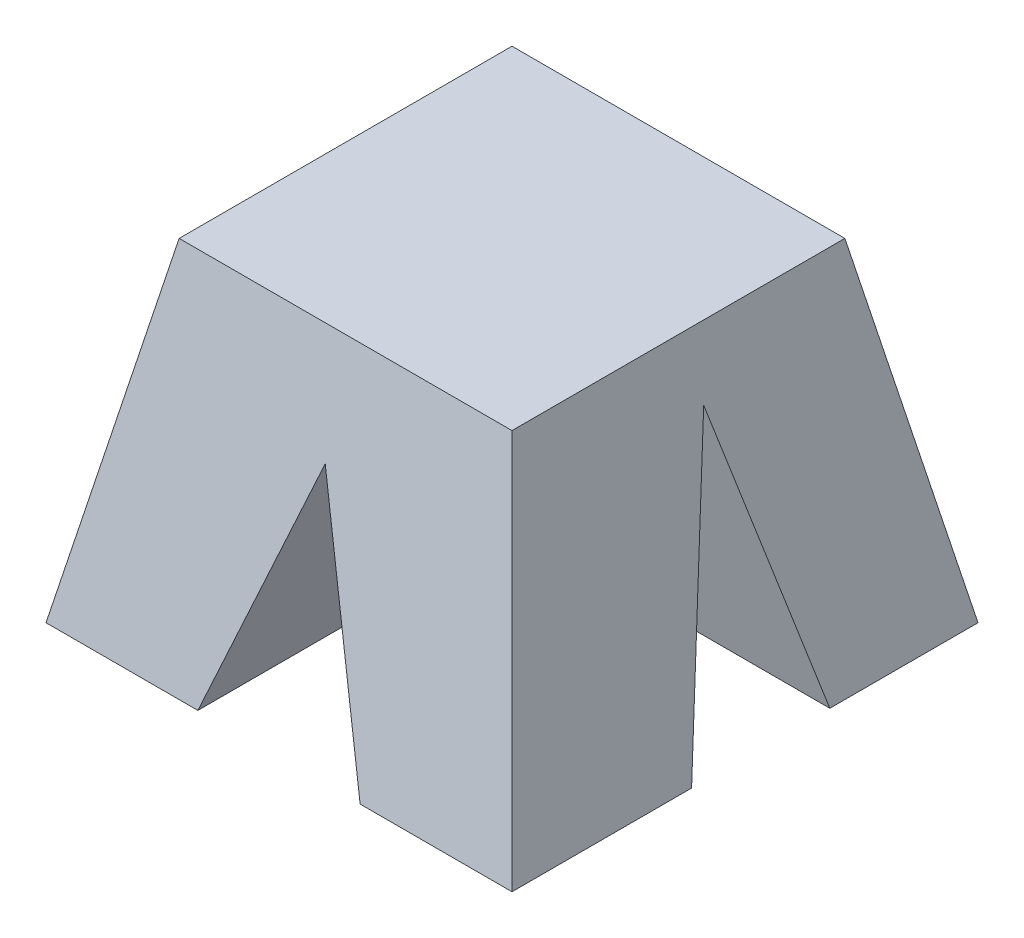
SolidWorks part; units mm, degrees
ref_plane "Front Plane" through (0, 0, 0) normal (0, 0, 1) x (1, 0, 0)
ref_plane "Top Plane" through (0, 0, 0) normal (0, 1, 0) x (1, 0, 0)
ref_plane "Right Plane" through (0, 0, 0) normal (1, 0, 0) x (0, 0, -1)
ref_plane "Plane4" through (0, -3, 0) normal (0, 1, 0) x (1, 0, 0)
ref_plane "Plane5" through (0, -5, 0) normal (0, 1, 0) x (1, 0, 0)
sketch "Sketch2" plane through (0, -3, 0) normal (0, -1, 0) x (1, 0, 0)
  line L1 (-1, 2) -> (1, 2)
  line L2 (-1, 2) -> (-1, 0)
  line L3 (-1, 0) -> (1, 0)
  line L4 (1, 2) -> (1, 0)
  dimension "D1" = 2
  dimension "D2" = 2
  dimension "D3" = 1
sketch "Sketch3" plane through (0, -5, 0) normal (0, -1, 0) x (-1, 0, 0)
  line L1 (-1.4, 0.4) -> (1.4, 0.4)
  line L2 (-1.4, 0.4) -> (-1.4, -2.4)
  line L3 (-1.4, -2.4) -> (1.4, -2.4)
  line L4 (1.4, 0.4) -> (1.4, -2.4)
  dimension "D1" = 2.8
  dimension "D2" = 2.8
  dimension "D3" = 1.4
  dimension "D4" = 0.4
loft "Loft1" add profiles "Sketch2", "Sketch3" connector at (-1, -3, 0) connector at (-1.4, -5, -0.4)
ref_plane "Plane2" through (0, 0, 3) normal (0, 0, 1) x (1, 0, 0)
sketch "Sketch4" plane through (0, 0, 3) normal (0, 0, 1) x (1, 0, 0)
  line L0 (0, -3.6115) -> (-0.5, -5.0359)
  line L2 (-0.5, -5.0359) -> (0.5, -5.0359)
  line L3 (0.5, -5.0359) -> (0, -3.6115)
  dimension "D1" = 0.5
  dimension "D2" = 0.5
  dimension "D3" = 3.6115
ref_plane "Plane3" through (1.8, 0, 0) normal (1, 0, 0) x (0, 0, -1)
sketch "Sketch7" plane through (1.8, 0, 0) normal (1, 0, 0) x (0, 0, -1)
  line L0 (-0.3952, -5.3589) -> (-0.9223, -3.3705)
  line L1 (-0.9223, -3.3705) -> (-1.444, -5.503)
  line L2 (-1.444, -5.503) -> (-0.3952, -5.3589)
extrude "Cut-Extrude1" cut sketch "Sketch7" against normal up to vertex (3.2 mm away) up to point (-1.4, -5, -0.4)
extrude "Cut-Extrude2" cut sketch "Sketch4" against normal up to vertex (3.4 mm away) up to point (-1.4, -5, -0.4)
equation "\"D3@Sketch3\"=\"D1@Sketch3\"/2"
equation "\"D4@Sketch3\"=(\"D2@Sketch3\"-2)/2"
